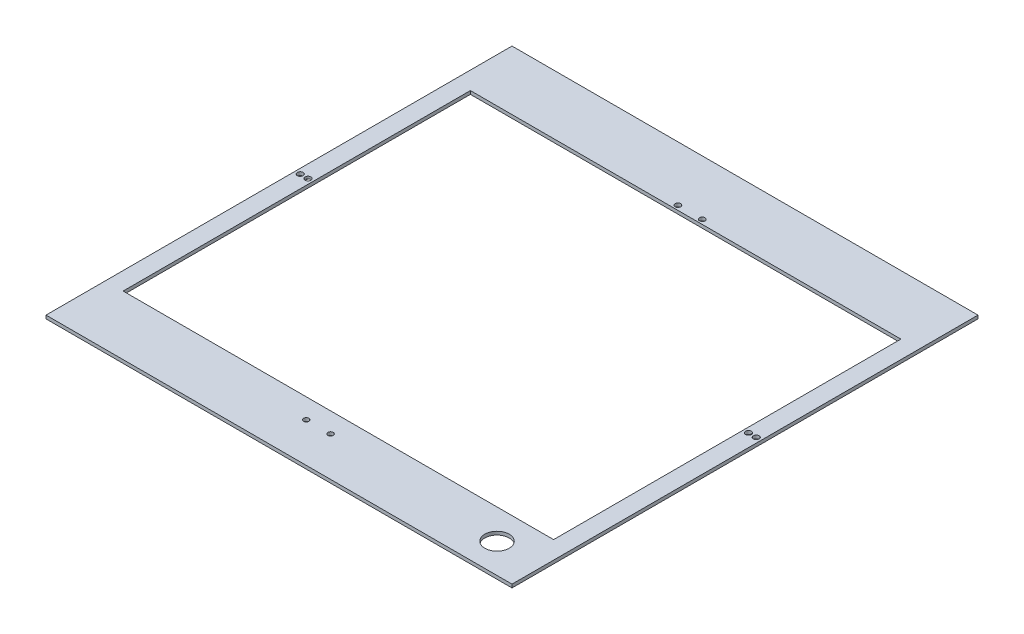
SolidWorks part; units mm, degrees
ref_plane "Front Plane" through (0, 0, 0) normal (0, 0, 1) x (1, 0, 0)
ref_plane "Top Plane" through (0, 0, 0) normal (0, 1, 0) x (1, 0, 0)
ref_plane "Right Plane" through (0, 0, 0) normal (1, 0, 0) x (0, 0, -1)
sketch "Sketch1" plane through (0, 0, 0) normal (0, 1, 0) x (1, 0, 0)
  line L1 (-210, -210) -> (210, -210)
  line L2 (-210, -210) -> (-210, 210)
  line L3 (-210, 210) -> (210, 210)
  line L4 (210, -210) -> (210, 210)
  line L5 (-210, -210) -> (210, 210) construction
  line L6 (-210, 210) -> (210, -210) construction
  line L7 (-194, 156.5) -> (194, 156.5)
  line L8 (-194, 156.5) -> (-194, -156.5)
  line L9 (-194, -156.5) -> (194, -156.5)
  line L10 (194, 156.5) -> (194, -156.5)
  line L11 (-194, 156.5) -> (194, -156.5) construction
  line L12 (-194, -156.5) -> (194, 156.5) construction
  circle A0 centre (169.75, -183.25) radius 11
  point P0 (0, 0)
  point P5 (0, 0)
  dimension "D5" = 22
  dimension "D1" = 420
  dimension "D2" = 420
  dimension "D3" = 313
  dimension "D4" = 388
extrude "Boss-Extrude1" add sketch "Sketch1" along normal blind 3
sketch "Sketch2" plane through (0, 0, 0) normal (0, -1, 0) x (1, 0, 0)
  line L0 (-210, 232.7824) -> (-210, -294.5834) construction
  line L1 (-210, -294.5834) -> (-202, -294.5834) construction
  line L2 (-202, -294.5834) -> (-202, 232.7824) construction
  line L3 (-202, 232.7824) -> (-210, 232.7824) construction
  line L4 (202, 232.7824) -> (202, -294.5834) construction
  line L5 (202, -294.5834) -> (210, -294.5834) construction
  line L6 (210, -294.5834) -> (210, 232.7824) construction
  line L7 (210, 232.7824) -> (202, 232.7824) construction
  line L8 (-197.5, 162.5) -> (-197.5, -162.5) construction
  line L9 (-197.5, -162.5) -> (197.5, -162.5) construction
  line L10 (197.5, -162.5) -> (197.5, 162.5) construction
  line L11 (197.5, 162.5) -> (-197.5, 162.5) construction
  line L12 (-210, 232.7824) -> (-210, -294.5834)
  line L13 (-210, -294.5834) -> (-202, -294.5834)
  line L14 (-202, -294.5834) -> (-202, 232.7824)
  line L15 (-202, 232.7824) -> (-210, 232.7824)
  line L16 (202, 232.7824) -> (202, -294.5834)
  line L17 (202, -294.5834) -> (210, -294.5834)
  line L18 (210, -294.5834) -> (210, 232.7824)
  line L19 (210, 232.7824) -> (202, 232.7824)
  line L20 (-197.5, 162.5) -> (-197.5, -162.5)
  line L21 (-197.5, -162.5) -> (197.5, -162.5)
  line L22 (197.5, -162.5) -> (197.5, 162.5)
  line L23 (197.5, 162.5) -> (-197.5, 162.5)
  line L24 (197.5, -162.5) -> (202, -167) construction
  line L25 (0, 0) -> (0, -113.1665) construction
  line L26 (0, 0) -> (113.3083, 0) construction
  line L27 (197.5, 162.5) -> (202, 167) construction
  line L28 (-197.5, 162.5) -> (-202, 167) construction
  line L29 (-197.5, -162.5) -> (-202, -167) construction
  line L30 (199.75, -164.75) -> (-199.75, -164.75)
  line L31 (-199.75, -164.75) -> (-199.75, 164.75)
  line L32 (-199.75, 164.75) -> (199.75, 164.75)
  line L33 (199.75, 164.75) -> (199.75, -164.75)
  line L34 (201.25, 166.25) -> (201.25, -166.25)
  line L35 (201.25, -166.25) -> (-201.25, -166.25)
  line L36 (-201.25, -166.25) -> (-201.25, 166.25)
  line L37 (-201.25, 166.25) -> (201.25, 166.25)
  line L38 (198.25, 163.25) -> (198.25, -163.25)
  line L39 (198.25, -163.25) -> (-198.25, -163.25)
  line L40 (-198.25, -163.25) -> (-198.25, 163.25)
  line L41 (-198.25, 163.25) -> (198.25, 163.25)
  dimension "D1" = 45
  dimension "D2" = 1.5
  dimension "D3" = 1.5
extrude "Cut-Extrude1" cut sketch "Sketch2" against normal blind 1 contours L37 L36 L35 L34 L32 L33 L30 L31 | L33 L32 L31 L30 L40 L41 L38 L39 region at (0, 0, -164.2321) region at (200.7279, 0, 0)
sketch "Sketch5" plane through (0, 3, 0) normal (0, 1, 0) x (1, 0, 0)
  line L0 (-205.5, 14.63) -> (-198.5, 14.63) construction
  line L1 (-194, 0) -> (-210, 0) construction
  line L2 (-194, 156.5) -> (-194, -156.5) construction
  line L3 (-202, 14.63) -> (-202, 0) construction
  line L4 (210, -210) -> (210, 210)
  line L5 (-210, -210) -> (210, -210)
  line L6 (-210, 210) -> (-210, -210)
  line L7 (210, 210) -> (-210, 210)
  line L8 (210, -210) -> (210, 210)
  line L9 (-210, -210) -> (210, -210)
  line L10 (-210, 210) -> (-210, -210)
  line L11 (210, 210) -> (-210, 210)
  line L12 (0, 156.5) -> (0, -156.5) construction
  line L13 (194, 156.5) -> (-194, 156.5) construction
  line L14 (-194, -156.5) -> (194, -156.5) construction
  line L15 (-11, 160.5) -> (11, 160.5) construction
  line L16 (0, 160.5) -> (0, 156.5) construction
  line L17 (-11, -174.5) -> (11, -174.5) construction
  line L18 (0, -174.5) -> (0, -156.5) construction
  circle A6 centre (-205.5, 14.63) radius 2.6
  circle A7 centre (-198.5, 14.63) radius 2.6
  circle A8 centre (198.5, 14.63) radius 2.6
  circle A9 centre (205.5, 14.63) radius 2.6
  circle A10 centre (-11, 160.5) radius 2.5
  circle A11 centre (11, 160.5) radius 2.5
  circle A12 centre (-11, -174.5) radius 2.4
  circle A13 centre (11, -174.5) radius 2.4
  point P34 (0, 0)
  dimension "D2" = 5.2
  dimension "D4" = 7
  dimension "D6" = 5
  dimension "D3" = 5.2
  dimension "D7" = 5
  dimension "D11" = 4.8
  dimension "D12" = 4.8
  dimension "D5" = 14.63
  dimension "D8" = 22
  dimension "D9" = 22
  dimension "D10" = 4
  dimension "D13" = 22
  dimension "D14" = 18
  dimension "D1" = 0
extrude "Cut-Extrude8" cut sketch "Sketch5" against normal through all contours A8 | A9 | A6 | A7 | A10 | A12 | A13 | A11 region at (-205.5, 3, -14.63) region at (-198.5, 3, -14.63) region at (198.5, 3, -14.63) region at (205.5, 3, -14.63) region at (-11, 3, -160.5) region at (11, 3, -160.5) region at (-11, 3, 174.5) region at (11, 3, 174.5)
